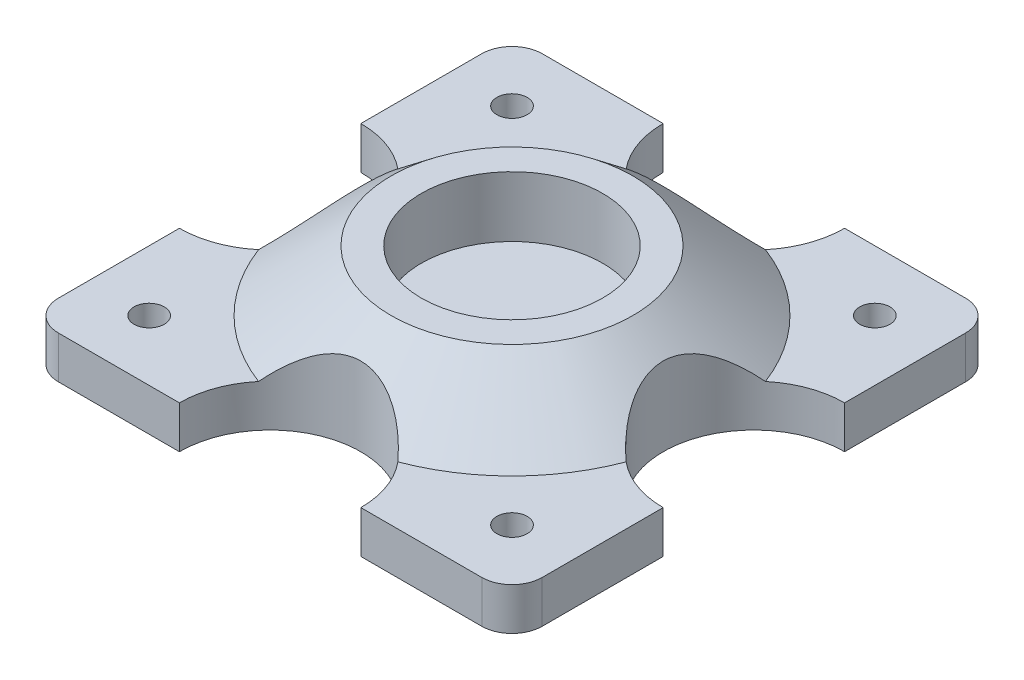
SolidWorks part; units mm, degrees
ref_plane "Front Plane" through (0, 0, 0) normal (0, 0, 1) x (1, 0, 0)
ref_plane "Top Plane" through (0, 0, 0) normal (0, 1, 0) x (1, 0, 0)
ref_plane "Right Plane" through (0, 0, 0) normal (1, 0, 0) x (0, 0, -1)
sketch "Sketch1" plane through (0, 0, 0) normal (0, 1, 0) x (1, 0, 0)
  line L1 (-44.45, -50.8) -> (44.45, -50.8)
  line L2 (-50.8, -44.45) -> (-50.8, 44.45)
  line L3 (-44.45, 50.8) -> (44.45, 50.8)
  line L4 (50.8, -44.45) -> (50.8, 44.45)
  line L5 (-50.8, -50.8) -> (50.8, 50.8) construction
  line L6 (-50.8, 50.8) -> (50.8, -50.8) construction
  arc A0 (44.45, -50.8) -> (50.8, -44.45) centre (44.45, -44.45) ccw
  arc A1 (44.45, 50.8) -> (50.8, 44.45) centre (44.45, 44.45) cw
  arc A2 (-44.45, -50.8) -> (-50.8, -44.45) centre (-44.45, -44.45) cw
  arc A3 (-50.8, 44.45) -> (-44.45, 50.8) centre (-44.45, 44.45) cw
  point P0 (0, 0)
  dimension "D3" = 6.35
  dimension "D1" = 101.6
  dimension "D2" = 101.6
extrude "Boss-Extrude1" add sketch "Sketch1" along normal blind 8.89
sketch "Sketch2" plane through (0, 0, 0) normal (0, 0, 1) x (1, 0, 0)
  line L0 (0, 21.59) -> (0, 8.89)
  line L1 (0, 21.59) -> (25.4, 21.59)
  line L2 (25.4, 21.59) -> (41.275, 8.89)
  line L3 (-44.45, 8.89) -> (44.45, 8.89) construction
  line L4 (41.275, 8.89) -> (0, 8.89)
  line L5 (0, -26.6582) -> (0, 42.3738) construction
  dimension "D1" = 12.7
  dimension "D2" = 50.8
  dimension "D3" = 82.55
revolve "Revolve1" add sketch "Sketch2" angle 360 about L5
sketch "Sketch3" plane through (0, 21.59, 0) normal (0, 1, 0) x (1, 0, 0)
  line L0 (50.8, -44.45) -> (50.8, 44.45) construction
  line L1 (44.45, 50.8) -> (-44.45, 50.8) construction
  line L2 (-50.8, 44.45) -> (-50.8, -44.45) construction
  line L3 (-44.45, -50.8) -> (44.45, -50.8) construction
  line L4 (0, -77.9804) -> (0, 73.5638) construction
  line L5 (-79.181, 0) -> (80.3683, 0) construction
  circle A0 centre (0, 0) radius 19.05
  circle A1 centre (50.8, 0) radius 19.05
  circle A2 centre (0, 50.8) radius 19.05
  circle A3 centre (-50.8, 0) radius 19.05
  circle A4 centre (0, -50.8) radius 19.05
  circle A5 centre (-38.1, 38.1) radius 3.175
  circle A6 centre (38.1, 38.1) radius 3.175
  circle A7 centre (38.1, -38.1) radius 3.175
  circle A8 centre (-38.1, -38.1) radius 3.175
  point P31 (0, 0)
  dimension "D1" = 38.1
  dimension "D2" = 38.1
  dimension "D3" = 6.35
  dimension "D5" = 76.2
  dimension "D4" = 76.2
extrude "Cut-Extrude1" cut sketch "Sketch3" against normal through all contours A3 | A2 | A4 | A1 | A7 | A6 | A5 | A8 region at (50.8, 21.59, 0) region at (0, 21.59, -50.8) region at (-50.8, 21.59, 0) region at (0, 21.59, 50.8) region at (-38.1, 21.59, -38.1) region at (38.1, 21.59, -38.1) region at (38.1, 21.59, 38.1) region at (-38.1, 21.59, 38.1)
extrude "Cut-Extrude2" cut sketch "Sketch3<3>" against normal up to surface (12.7 mm away) contours A0 region at (0, 21.59, 0) up to face at (-37.1493, 8.89, 37.1493)
sketch "Sketch3<3>" plane through (0, 21.59, 0) normal (0, 1, 0) x (1, 0, 0) same geometry as "Sketch3"
